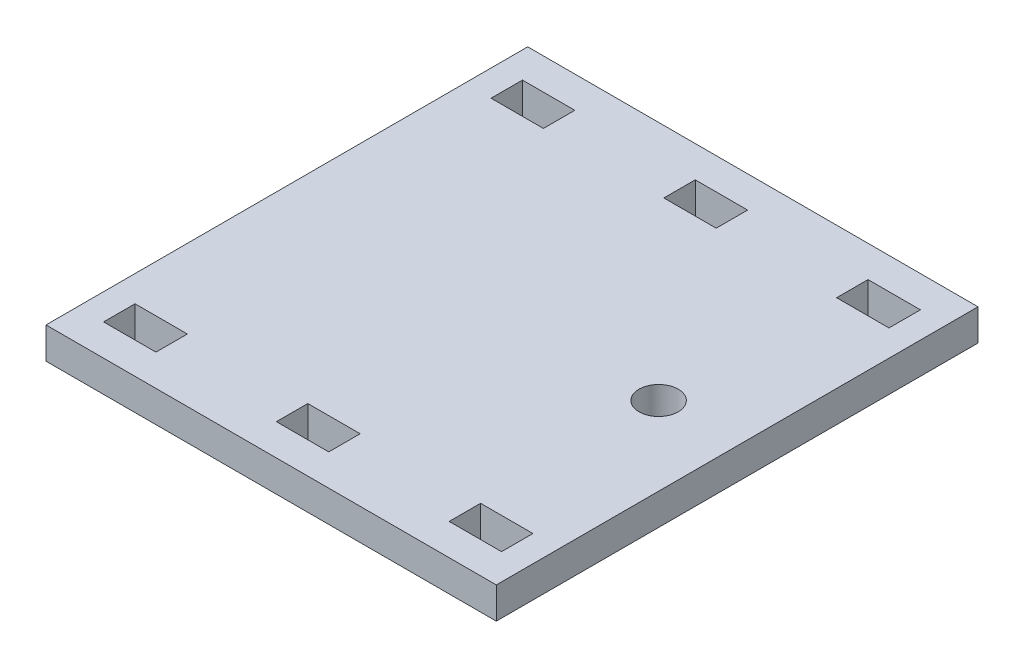
SolidWorks part; units mm, degrees
material "Maple"
ref_plane "Front Plane" through (0, 0, 0) normal (0, 0, 1) x (1, 0, 0)
ref_plane "Top Plane" through (0, 0, 0) normal (0, 1, 0) x (1, 0, 0)
ref_plane "Right Plane" through (0, 0, 0) normal (1, 0, 0) x (0, 0, -1)
sketch "Sketch1" plane through (0, 0, 0) normal (0, 1, 0) x (1, 0, 0)
  line L0 (86, -181.1) -> (86, 120.4) construction
  line L1 (0, 0) -> (86, 0)
  line L2 (0, 0) -> (0, 92)
  line L3 (0, 92) -> (86, 92)
  line L4 (86, 0) -> (86, 92)
  dimension "D2" = 92
extrude "Boss-Extrude1" add sketch "Sketch1" along normal blind 6
ref_plane "Plane1" through (0, 3, 0) normal (0, 1, 0) x (1, 0, 0)
ref_plane "Plane2" through (0, 0, -46) normal (0, 0, 1) x (1, 0, 0)
hole_wizard "Ø7.5 (7.5) Diameter Hole1" positions "Sketch3" profile "Sketch2" hole size "Ø7.5" standard "ANSI Metric" end condition through all
sketch "Sketch3" plane through (0, 6, 0) normal (0, 1, 0) x (1, 0, 0)
  circle A0 centre (71, 46) radius 4 construction
  point P0 (71, 46)
sketch "Sketch2" plane through (71, 6, -46) normal (1, 0, 0) x (0, 0, 1)
  line L0 (0, 0) -> (0, 6)
  line L1 (0, 6) -> (3.75, 6)
  line L2 (3.75, 6) -> (3.75, 0)
  line L5 (3.75, 0) -> (0, 0)
  line L11 (0, -6.35) -> (0, 107.95) construction
  dimension "Thru Hole Dia." = 7.5
  dimension "Thru Hole Depth" = 6
sketch "Sketch4" plane through (0, 0, 0) normal (0, -1, 0) x (1, 0, 0)
  line L0 (0, -9) -> (86, -9) construction
  line L1 (0, -92) -> (0, 0) construction
  line L2 (86, 0) -> (86, -92) construction
  line L3 (25.85, -9) -> (-25.85, -9) construction
  line L4 (10, -9) -> (43, -9) construction
  line L5 (0, -23) -> (86, -23) construction
  line L6 (4.4, -23) -> (-4.4, -23) construction
  line L7 (10, -23) -> (43, -23) construction
  point P8 (10, -9)
  point P11 (43, -9)
  point P12 (76, -9)
  point P17 (10, -23)
  point P19 (43, -23)
  point P20 (76, -23)
  dimension "D2" = 10
  dimension "D3" = 10
  dimension "D5" = 10
  dimension "D6" = 10
  dimension "D1" = 3
  dimension "D4" = 3
sketch "Sketch6" plane through (9.2322, 3, 35) normal (0, -1, 0) x (1, 0, 0)
  line L1 (-4.2322, -41) -> (5.7678, -41)
  line L2 (-4.2322, -41) -> (-4.2322, -47)
  line L3 (-4.2322, -47) -> (5.7678, -47)
  line L4 (5.7678, -41) -> (5.7678, -47)
  line L5 (-4.2322, -41) -> (5.7678, -47) construction
  line L6 (-4.2322, -47) -> (5.7678, -41) construction
  point P0 (0.7678, -44)
  dimension "D1" = 10
  dimension "D2" = 6
extrude "Cut-Extrude1" cut sketch "Sketch6" against normal through all and the other way through all
other "Smart-Feature1<virtual_pin-24>" [suppressed]
sketch "Sketch61" plane through (42.2322, 3, 35) normal (0, -1, 0) x (1, 0, 0)
  line L1 (-4.2322, -41) -> (5.7678, -41)
  line L2 (-4.2322, -41) -> (-4.2322, -47)
  line L3 (-4.2322, -47) -> (5.7678, -47)
  line L4 (5.7678, -41) -> (5.7678, -47)
  line L5 (-4.2322, -41) -> (5.7678, -47) construction
  line L6 (-4.2322, -47) -> (5.7678, -41) construction
  point P0 (0.7678, -44)
  dimension "D1" = 10
  dimension "D2" = 6
extrude "Cut-Extrude11" cut sketch "Sketch61" against normal through all and the other way through all
other "Smart-Feature2<virtual_pin-25>" [suppressed]
sketch "Sketch62" plane through (75.2322, 3, 35) normal (0, -1, 0) x (1, 0, 0)
  line L1 (-4.2322, -41) -> (5.7678, -41)
  line L2 (-4.2322, -41) -> (-4.2322, -47)
  line L3 (-4.2322, -47) -> (5.7678, -47)
  line L4 (5.7678, -41) -> (5.7678, -47)
  line L5 (-4.2322, -41) -> (5.7678, -47) construction
  line L6 (-4.2322, -47) -> (5.7678, -41) construction
  point P0 (0.7678, -44)
  dimension "D1" = 10
  dimension "D2" = 6
extrude "Cut-Extrude12" cut sketch "Sketch62" against normal through all and the other way through all
other "Smart-Feature3<virtual_pin-26>" [suppressed]
sketch "Sketch64" plane through (9.2322, 3, 21) normal (0, -1, 0) x (1, 0, 0)
  line L1 (-4.2322, -41) -> (5.7678, -41)
  line L2 (-4.2322, -41) -> (-4.2322, -47)
  line L3 (-4.2322, -47) -> (5.7678, -47)
  line L4 (5.7678, -41) -> (5.7678, -47)
  line L5 (-4.2322, -41) -> (5.7678, -47) construction
  line L6 (-4.2322, -47) -> (5.7678, -41) construction
  point P0 (0.7678, -44)
  dimension "D1" = 10
  dimension "D2" = 6
extrude "Cut-Extrude14" [suppressed] cut sketch "Sketch64" against normal through all and the other way through all
other "Smart-Feature1<virtual_pin-27>" [suppressed]
sketch "Sketch65" plane through (42.2322, 3, 21) normal (0, -1, 0) x (1, 0, 0)
  line L1 (-4.2322, -41) -> (5.7678, -41)
  line L2 (-4.2322, -41) -> (-4.2322, -47)
  line L3 (-4.2322, -47) -> (5.7678, -47)
  line L4 (5.7678, -41) -> (5.7678, -47)
  line L5 (-4.2322, -41) -> (5.7678, -47) construction
  line L6 (-4.2322, -47) -> (5.7678, -41) construction
  point P0 (0.7678, -44)
  dimension "D1" = 10
  dimension "D2" = 6
extrude "Cut-Extrude15" [suppressed] cut sketch "Sketch65" against normal through all and the other way through all
other "Smart-Feature2<virtual_pin-28>" [suppressed]
sketch "Sketch66" plane through (75.2322, 3, 21) normal (0, -1, 0) x (1, 0, 0)
  line L1 (-4.2322, -41) -> (5.7678, -41)
  line L2 (-4.2322, -41) -> (-4.2322, -47)
  line L3 (-4.2322, -47) -> (5.7678, -47)
  line L4 (5.7678, -41) -> (5.7678, -47)
  line L5 (-4.2322, -41) -> (5.7678, -47) construction
  line L6 (-4.2322, -47) -> (5.7678, -41) construction
  point P0 (0.7678, -44)
  dimension "D1" = 10
  dimension "D2" = 6
extrude "Cut-Extrude16" [suppressed] cut sketch "Sketch66" against normal through all and the other way through all
other "Smart-Feature3<virtual_pin-29>" [suppressed]
mirror "Mirror1" about plane through (0, 0, -46) normal (0, 0, 1) of "Cut-Extrude1", "Cut-Extrude11", "Cut-Extrude12", "Cut-Extrude16", "Cut-Extrude15", "Cut-Extrude14"
